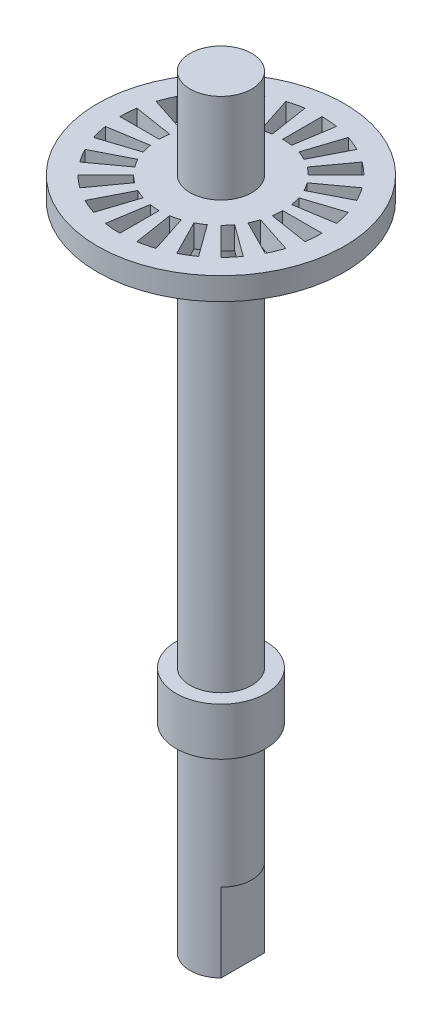
SolidWorks part; units mm, degrees
ref_plane "前视基准面" through (0, 0, 0) normal (0, 0, 1) x (1, 0, 0)
ref_plane "上视基准面" through (0, 0, 0) normal (0, 1, 0) x (1, 0, 0)
ref_plane "右视基准面" through (0, 0, 0) normal (1, 0, 0) x (0, 0, -1)
sketch "草图1" plane through (0, 0, 0) normal (0, 1, 0) x (1, 0, 0)
  circle A0 centre (0, 0) radius 2.75
  dimension "D1" = 5.5
extrude "凸台-拉伸1" add sketch "草图1" along normal blind 61
sketch "草图2" plane through (0, 0, 0) normal (0, -1, 0) x (1, 0, 0)
  line L0 (0, 0) -> (0, -4.8851) construction
  line L2 (-1.95, 1.9391) -> (-1.95, -1.9391)
  line L4 (1.95, 1.9391) -> (1.95, -1.9391)
  arc A0 (-1.95, -1.9391) -> (1.95, -1.9391) centre (0, 0) ccw
  arc A1 (1.95, 1.9391) -> (-1.95, 1.9391) centre (0, 0) ccw
  dimension "D1" = 5.5
  dimension "D2" = 3.9
extrude "凸台-拉伸2" add sketch "草图2" along normal blind 7
sketch "草图3" plane through (0, -7, 0) normal (0, -1, 0) x (1, 0, 0)
  circle A0 centre (0, 0) radius 4
  dimension "D1" = 8
extrude "凸台-拉伸3" add sketch "草图3" along normal blind 4.25 from offset 22 offset against normal yes
sketch "草图4" plane through (0, 0, 0) normal (0, 0, 1) x (1, 0, 0)
  circle A0 centre (0, 46.3457) radius 0.375
  dimension "D1" = 0.75
extrude "切除-拉伸1" cut sketch "草图4" against normal mid plane 10
sketch "草图6" plane through (0, 61, 0) normal (0, 1, 0) x (1, 0, 0)
  line L0 (0, 9) -> (0, 5.5)
  line L1 (1.4079, 8.8892) -> (0.8604, 5.4323)
  line L2 (0, 5.5) -> (0, 0) construction
  line L3 (0.8604, 5.4323) -> (0, 0) construction
  line L4 (2.7812, 8.5595) -> (1.6996, 5.2308)
  line L5 (4.0859, 8.0191) -> (2.4969, 4.9005)
  line L6 (5.2901, 7.2812) -> (3.2328, 4.4496)
  line L7 (6.364, 6.364) -> (3.8891, 3.8891)
  line L8 (7.2812, 5.2901) -> (4.4496, 3.2328)
  line L9 (8.0191, 4.0859) -> (4.9005, 2.4969)
  line L10 (8.5595, 2.7812) -> (5.2308, 1.6996)
  line L11 (8.8892, 1.4079) -> (5.4323, 0.8604)
  line L12 (9, 0) -> (5.5, 0)
  line L13 (8.8892, -1.4079) -> (5.4323, -0.8604)
  line L14 (8.5595, -2.7812) -> (5.2308, -1.6996)
  line L15 (8.0191, -4.0859) -> (4.9005, -2.4969)
  line L16 (7.2812, -5.2901) -> (4.4496, -3.2328)
  line L17 (6.364, -6.364) -> (3.8891, -3.8891)
  line L18 (5.2901, -7.2812) -> (3.2328, -4.4496)
  line L19 (4.0859, -8.0191) -> (2.4969, -4.9005)
  line L20 (2.7812, -8.5595) -> (1.6996, -5.2308)
  line L21 (1.4079, -8.8892) -> (0.8604, -5.4323)
  line L22 (0, -9) -> (0, -5.5)
  line L23 (-1.4079, -8.8892) -> (-0.8604, -5.4323)
  line L24 (-2.7812, -8.5595) -> (-1.6996, -5.2308)
  line L25 (-4.0859, -8.0191) -> (-2.4969, -4.9005)
  line L26 (-5.2901, -7.2812) -> (-3.2328, -4.4496)
  line L27 (-6.364, -6.364) -> (-3.8891, -3.8891)
  line L28 (-7.2812, -5.2901) -> (-4.4496, -3.2328)
  line L29 (-8.0191, -4.0859) -> (-4.9005, -2.4969)
  line L30 (-8.5595, -2.7812) -> (-5.2308, -1.6996)
  line L31 (-8.8892, -1.4079) -> (-5.4323, -0.8604)
  line L32 (-9, 0) -> (-5.5, 0)
  line L33 (-8.8892, 1.4079) -> (-5.4323, 0.8604)
  line L34 (-8.5595, 2.7812) -> (-5.2308, 1.6996)
  line L35 (-8.0191, 4.0859) -> (-4.9005, 2.4969)
  line L36 (-7.2812, 5.2901) -> (-4.4496, 3.2328)
  line L37 (-6.364, 6.364) -> (-3.8891, 3.8891)
  line L38 (-5.2901, 7.2812) -> (-3.2328, 4.4496)
  line L39 (-4.0859, 8.0191) -> (-2.4969, 4.9005)
  line L40 (-2.7812, 8.5595) -> (-1.6996, 5.2308)
  line L41 (-1.4079, 8.8892) -> (-0.8604, 5.4323)
  circle A0 centre (0, 0) radius 11
  arc A3 (0, 5.5) -> (0.8604, 5.4323) centre (0, 0) cw
  arc A4 (0, 9) -> (1.4079, 8.8892) centre (0, 0) cw
  arc A5 (1.6996, 5.2308) -> (2.4969, 4.9005) centre (0, 0) cw
  arc A6 (2.7812, 8.5595) -> (4.0859, 8.0191) centre (0, 0) cw
  arc A7 (3.2328, 4.4496) -> (3.8891, 3.8891) centre (0, 0) cw
  arc A8 (5.2901, 7.2812) -> (6.364, 6.364) centre (0, 0) cw
  arc A9 (4.4496, 3.2328) -> (4.9005, 2.4969) centre (0, 0) cw
  arc A10 (7.2812, 5.2901) -> (8.0191, 4.0859) centre (0, 0) cw
  arc A11 (5.2308, 1.6996) -> (5.4323, 0.8604) centre (0, 0) cw
  arc A12 (8.5595, 2.7812) -> (8.8892, 1.4079) centre (0, 0) cw
  arc A13 (5.5, 0) -> (5.4323, -0.8604) centre (0, 0) cw
  arc A14 (9, 0) -> (8.8892, -1.4079) centre (0, 0) cw
  arc A15 (5.2308, -1.6996) -> (4.9005, -2.4969) centre (0, 0) cw
  arc A16 (8.5595, -2.7812) -> (8.0191, -4.0859) centre (0, 0) cw
  arc A17 (4.4496, -3.2328) -> (3.8891, -3.8891) centre (0, 0) cw
  arc A18 (7.2812, -5.2901) -> (6.364, -6.364) centre (0, 0) cw
  arc A19 (3.2328, -4.4496) -> (2.4969, -4.9005) centre (0, 0) cw
  arc A20 (5.2901, -7.2812) -> (4.0859, -8.0191) centre (0, 0) cw
  arc A21 (1.6996, -5.2308) -> (0.8604, -5.4323) centre (0, 0) cw
  arc A22 (2.7812, -8.5595) -> (1.4079, -8.8892) centre (0, 0) cw
  arc A23 (0, -5.5) -> (-0.8604, -5.4323) centre (0, 0) cw
  arc A24 (0, -9) -> (-1.4079, -8.8892) centre (0, 0) cw
  arc A25 (-1.6996, -5.2308) -> (-2.4969, -4.9005) centre (0, 0) cw
  arc A26 (-2.7812, -8.5595) -> (-4.0859, -8.0191) centre (0, 0) cw
  arc A27 (-3.2328, -4.4496) -> (-3.8891, -3.8891) centre (0, 0) cw
  arc A28 (-5.2901, -7.2812) -> (-6.364, -6.364) centre (0, 0) cw
  arc A29 (-4.4496, -3.2328) -> (-4.9005, -2.4969) centre (0, 0) cw
  arc A30 (-7.2812, -5.2901) -> (-8.0191, -4.0859) centre (0, 0) cw
  arc A31 (-5.2308, -1.6996) -> (-5.4323, -0.8604) centre (0, 0) cw
  arc A32 (-8.5595, -2.7812) -> (-8.8892, -1.4079) centre (0, 0) cw
  arc A33 (-5.5, 0) -> (-5.4323, 0.8604) centre (0, 0) cw
  arc A34 (-9, 0) -> (-8.8892, 1.4079) centre (0, 0) cw
  arc A35 (-5.2308, 1.6996) -> (-4.9005, 2.4969) centre (0, 0) cw
  arc A36 (-8.5595, 2.7812) -> (-8.0191, 4.0859) centre (0, 0) cw
  arc A37 (-4.4496, 3.2328) -> (-3.8891, 3.8891) centre (0, 0) cw
  arc A38 (-7.2812, 5.2901) -> (-6.364, 6.364) centre (0, 0) cw
  arc A39 (-3.2328, 4.4496) -> (-2.4969, 4.9005) centre (0, 0) cw
  arc A40 (-5.2901, 7.2812) -> (-4.0859, 8.0191) centre (0, 0) cw
  arc A41 (-1.6996, 5.2308) -> (-0.8604, 5.4323) centre (0, 0) cw
  arc A42 (-2.7812, 8.5595) -> (-1.4079, 8.8892) centre (0, 0) cw
  point P86 (0, 0)
  dimension "D1" = 22
  dimension "D3" = 5.5
  dimension "D4" = 9
  dimension "D2" = 9
  dimension "D5" = 20
extrude "凸台-拉伸4" add sketch "草图6" along normal blind 2 from offset 10 offset against normal yes
